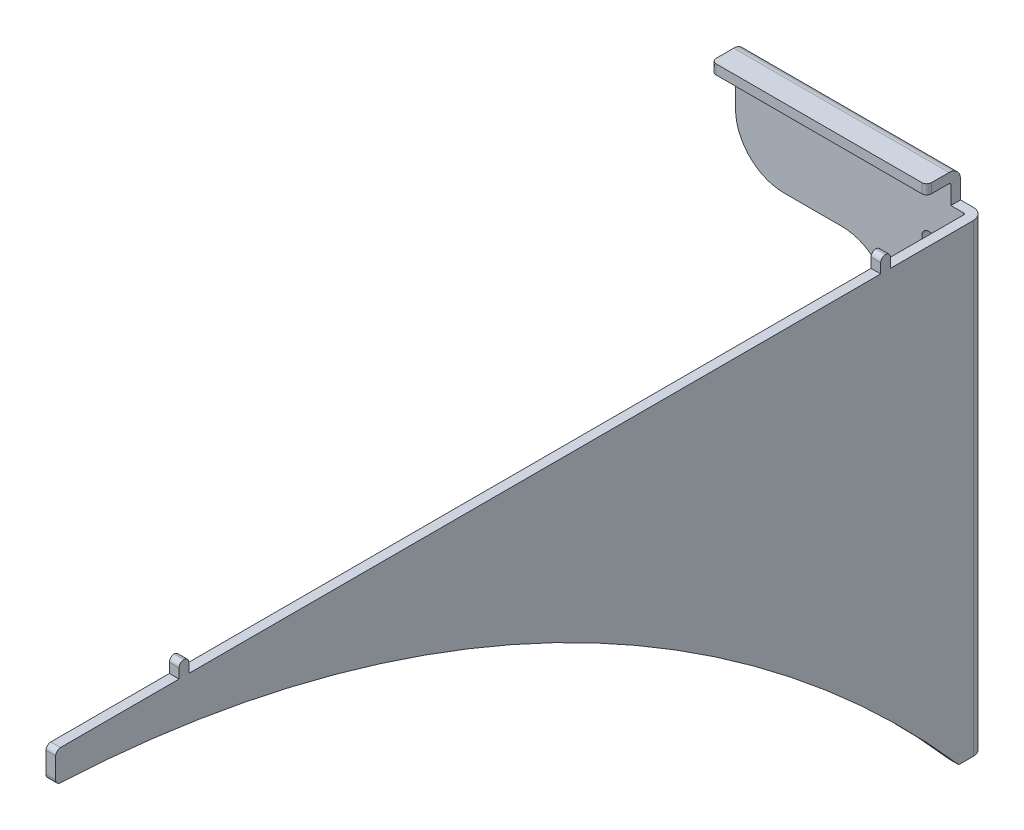
SolidWorks part; units mm, degrees
note: The reader was unsure of these and kept them because the rebuilt part matched: flange length of "Edge-Flange1", "Edge-Flange2", "Edge-Flange3".
material "6061 Alloy"
ref_plane "Front Plane" through (0, 0, 0) normal (0, 0, 1) x (1, 0, 0)
ref_plane "Top Plane" through (0, 0, 0) normal (0, 1, 0) x (1, 0, 0)
ref_plane "Right Plane" through (0, 0, 0) normal (1, 0, 0) x (0, 0, -1)
sketch "Sketch1" plane through (0, 0, 0) normal (0, 0, 1) x (1, 0, 0)
  line L1 (0, 0) -> (380, 0)
  line L2 (0, 0) -> (0, 200)
  line L3 (0, 200) -> (380, 200)
  line L4 (380, 0) -> (380, 200)
  dimension "D1" = 380
  dimension "D2" = 200
sheet metal parameters "Sheet-Metal1" thickness 4 parameters "D1"=0.7366
base flange "Base-Flange1" sketch "Sketch1" thickness 4 reverse thickness direction yes parameters "D1"=0.7366
edge flange "Edge-Flange1" sketch "Sketch5" flange angle 90 flange length 10 flange position material outside bend radius 0.7366 thickness 4 relief rectangular parameters "D6"=10
sketch "Sketch5" plane through (0, 200, 4) normal (0, 1, 0) x (-1, 0, 0)
  line L2 (-380, 0) -> (-380, 10)
  line L3 (-380, 10) -> (0, 10)
  line L4 (0, 10) -> (0, 0)
  line L5 (-380, 0) -> (0, 0) construction
  line L6 (-380, 0) -> (0, 0)
bend "EdgeBend1" bend radius 0.7366 bend angle 90 parameters "D5"=1
edge flange "Edge-Flange2" sketch "Sketch8" flange angle 90 flange length 380 flange position material outside bend radius 0.7366 thickness 4 relief none parameters "D6"=10
sketch "Sketch8" plane through (0, 0, 4) normal (-1, 0, 0) x (0, -1, 0)
  line L2 (-199.2634, 0) -> (-199.2634, 380)
  line L3 (-199.2634, 380) -> (0, 380)
  line L4 (0, 380) -> (0, 0)
  line L5 (-199.2634, 0) -> (0, 0) construction
  line L6 (-199.2634, 0) -> (0, 0)
bend "EdgeBend2" bend radius 0.7366 bend angle 90 parameters "D5"=2
edge flange "Edge-Flange3" sketch "Sketch11" flange angle 90 flange length 380 flange position material outside bend radius 0.7366 thickness 4 relief none parameters "D6"=10
sketch "Sketch11" plane through (380, 0, 4) normal (1, 0, 0) x (0, 1, 0)
  line L0 (0, 0) -> (199.2634, 0) construction
  line L1 (0, 0) -> (199.2634, 0)
  line L2 (0, 0) -> (0, 380)
  line L3 (0, 380) -> (199.2634, 380)
  line L4 (199.2634, 380) -> (199.2634, 0)
bend "EdgeBend3" bend radius 0.7366 bend angle 90 parameters "D5"=3
sketch "Sketch12" plane through (-4, 0, 0) normal (-1, 0, 0) x (0, 0, 1)
  line L0 (384, 0) -> (384, 199.2634) construction
  line L1 (4.7366, 0) -> (384, 0) construction
  line L2 (10.7366, 0) -> (384, 0)
  line L3 (384, 0) -> (384, 179.2634)
  line L4 (384, 199.2634) -> (4.7366, 199.2634) construction
  line L5 (4.7366, 0) -> (4.7366, 199.2634) construction
  arc A0 (10.7366, 0) -> (384, 179.2634) centre (407.2603, -347.4068) cw
  line M2 (4.7366, 0) -> (384, 0)
  line M3 (384, 0) -> (384, 199.2634)
  dimension "D1" = 6
  dimension "D2" = 20
extrude "Extrude1" cut sketch "Sketch12" against normal through all contours A0 M2 M3 normal cut yes
sketch "Sketch13" plane through (-4, 0, 0) normal (-1, 0, 0) x (0, 0, 1)
  line L0 (14.8578, 191.8) -> (38.9966, 191.8)
  line L1 (38.9966, 191.8) -> (38.9966, 197.8)
  line L2 (38.9966, 197.8) -> (42.9966, 197.8)
  line L3 (42.9966, 197.8) -> (42.9966, 191.8)
  line L4 (42.9966, 191.8) -> (328.9966, 191.8)
  line L5 (328.9966, 191.8) -> (328.9966, 197.8)
  line L6 (328.9966, 197.8) -> (332.9966, 197.8)
  line L7 (332.9966, 197.8) -> (332.9966, 191.8)
  line L8 (332.9966, 191.8) -> (384, 191.8)
  line L10 (384, 199.2634) -> (4.7366, 199.2634)
  line L11 (4.7366, 199.2634) -> (4.7366, 191.8)
  line L12 (4.7366, 0) -> (4.7366, 199.2634) construction
  line L13 (4.7366, 191.8) -> (14.8578, 191.8)
  line L14 (4.7366, 200) -> (14, 200) construction
  line L16 (384, 179.2634) -> (384, 199.2634) construction
  line L17 (384, 191.8) -> (384, 199.2634)
  dimension "D1" = 4
  dimension "D2" = 4
  dimension "D3" = 34.26
  dimension "D4" = 6
  dimension "D5" = 8.2
  dimension "D6" = 290
extrude "Extrude2" cut sketch "Sketch13" against normal through all normal cut yes
fillet "Fillet1" radius 2 8 edges at (382, 197.8, 38.9966) (382, 197.8, 42.9966) (382, 197.8, 328.9966) (382, 197.8, 332.9966) (-2, 197.8, 328.9966) (-2, 197.8, 332.9966) (-2, 197.8, 42.9966) (-2, 197.8, 38.9966)
sketch "Sketch15" plane through (-4, 0, 0) normal (-1, 0, 0) x (0, 0, 1)
  line L0 (38.9966, 191.8) -> (4.7366, 191.8) construction
  line L1 (20.5212, 191.8) -> (-2.9513, 191.8)
  line L2 (20.5212, 191.8) -> (20.5212, 225.0767)
  line L3 (20.5212, 225.0767) -> (-2.9513, 225.0767)
  line L4 (-2.9513, 191.8) -> (-2.9513, 225.0767)
extrude "Extrude6" cut sketch "Sketch15" against normal blind 10 normal cut yes
sketch "Sketch16" plane through (384, 0, 0) normal (1, 0, 0) x (0, 0, -1)
  line L0 (-4.7366, 191.8) -> (-38.9966, 191.8) construction
  line L1 (-19.1375, 191.8) -> (6.9156, 191.8)
  line L2 (-19.1375, 191.8) -> (-19.1375, 209.4983)
  line L3 (-19.1375, 209.4983) -> (6.9156, 209.4983)
  line L4 (6.9156, 191.8) -> (6.9156, 209.4983)
extrude "Extrude7" cut sketch "Sketch16" against normal blind 10 normal cut yes
fillet "Fillet2" radius 2 2 edges at (374, 202, 14) (6, 202, 14)
sketch "Sketch17" plane through (0, 0, 4) normal (0, 0, 1) x (1, 0, 0)
  line L0 (0.7366, 0) -> (379.2634, 0) construction
  line L1 (31, 161.8) -> (349, 161.8)
  line L2 (31, 161.8) -> (31, 0)
  line L3 (31, 0) -> (349, 0)
  line L4 (349, 161.8) -> (349, 0)
  line L5 (6, 191.8) -> (6, 199.2634) construction
  line L6 (374, 191.8) -> (374, 199.2634) construction
  line L7 (6, 191.8) -> (0.7366, 191.8) construction
  dimension "D1" = 25
  dimension "D2" = 25
  dimension "D3" = 30
extrude "Extrude8" cut sketch "Sketch17" against normal through all normal cut yes
fillet "Fillet3" radius 20 2 edges at (349, 161.8, 2) (31, 161.8, 2)
sketch "Sketch18" plane through (0, 0, 4) normal (0, 0, 1) x (1, 0, 0)
  line L0 (374, 200) -> (6, 200) construction
  line L1 (0, 191.8) -> (0, 0) construction
  circle A0 centre (15, 175) radius 3
  circle A1 centre (365, 175) radius 3
  dimension "D3" = 6
  dimension "D5" = 6
  dimension "D1" = 25
  dimension "D2" = 350
  dimension "D4" = 15
extrude "Extrude9" cut sketch "Sketch18" against normal through all normal cut yes
pattern_linear "LPattern1" count 17 spacing 10 along (0, -1, 0) of "Extrude9"
sketch "Sketch20" plane through (0, 0, 0) normal (0, 0, -1) x (-1, 0, 0)
  line L1 (-285, 278.9428) -> (515, 278.9428)
  line L2 (-285, 278.9428) -> (-285, -521.0572)
  line L3 (-285, -521.0572) -> (515, -521.0572)
  line L4 (515, 278.9428) -> (515, -521.0572)
  circle A0 centre (-365, 175) radius 3 construction
  dimension "D1" = 80
  dimension "D2" = 800
  dimension "D3" = 800
extrude "Extrude15" cut sketch "Sketch20" against normal through all normal cut yes
fillet "Fillet4" radius 20 1 edges at (285, 161.8, 2)
fillet "Fillet5" radius 2 1 edges at (285, 202, 14)
fillet "Fillet6" radius 2 2 edges at (382, 179.2634, 384) (382, 191.8, 384)
flat pattern "Flat-Pattern1" [suppressed]
sketch "Bend-Lines1" plane through (0, 0, 4) normal (0, 0, 1) x (1, 0, 0)
  line L0 (601.4127, 0) -> (601.4127, 191.8) construction
  line L1 (-1.4127, 0) -> (-1.4127, 191.8) construction
  line L2 (6, 201.4127) -> (594, 201.4127) construction
  line L3 (601.4127, 0) -> (601.4127, 191.8) construction
  line L4 (-1.4127, 0) -> (-1.4127, 191.8) construction
  line L5 (6, 201.4127) -> (594, 201.4127) construction
bend of the flat pattern "Flatten-<EdgeBend1>1"
bend of the flat pattern "Flatten-<EdgeBend2>1"
bend of the flat pattern "Flatten-<EdgeBend3>1"
